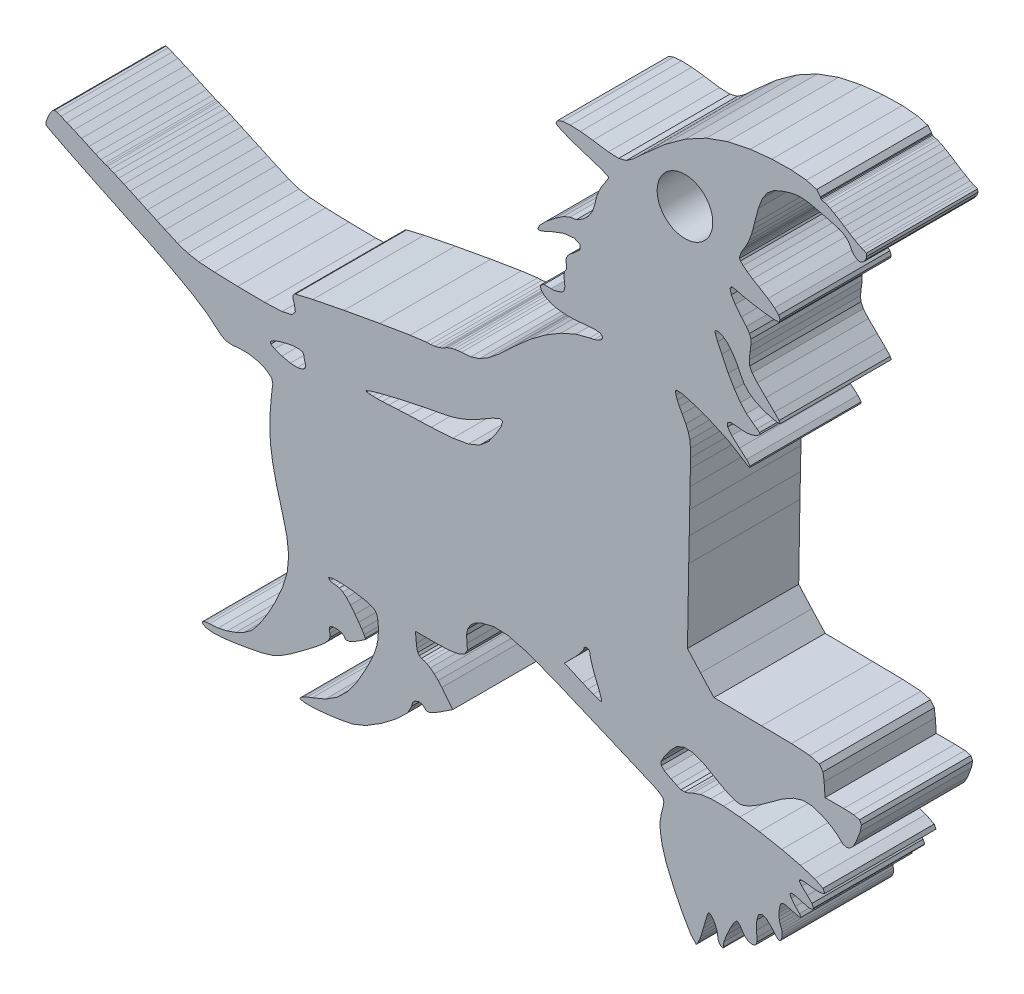
SolidWorks part; units mm, degrees
ref_plane "Plan de face" through (0, 0, 0) normal (0, 0, 1) x (1, 0, 0)
ref_plane "Plan de dessus" through (0, 0, 0) normal (0, 1, 0) x (1, 0, 0)
ref_plane "Plan de droite" through (0, 0, 0) normal (1, 0, 0) x (0, 0, -1)
sketch "Esquisse7" plane through (0, 0, 0) normal (0, 0, 1) x (1, 0, 0)
  line L0 (21.1015, 17.6172) -> (20.7585, 17.1388)
  line L1 (20.7585, 17.1388) -> (20.3691, 16.8087)
  line L2 (20.3691, 16.8087) -> (19.8602, 16.5976)
  line L3 (19.8602, 16.5976) -> (19.1586, 16.4758)
  line L4 (19.1586, 16.4758) -> (18.1909, 16.4138)
  line L5 (18.1909, 16.4138) -> (17.6884, 16.3956)
  line L6 (17.6884, 16.3956) -> (17.1798, 16.3753)
  line L7 (17.1798, 16.3753) -> (16.7028, 16.3544)
  line L8 (16.7028, 16.3544) -> (16.295, 16.3341)
  line L9 (16.295, 16.3341) -> (15.994, 16.3159)
  line L10 (15.994, 16.3159) -> (15.7611, 16.3109)
  line L11 (15.7611, 16.3109) -> (15.5577, 16.3134)
  line L12 (15.5577, 16.3134) -> (15.3966, 16.3239)
  line L13 (15.3966, 16.3239) -> (15.2906, 16.3432)
  line L14 (15.2906, 16.3432) -> (15.2524, 16.3718)
  line L15 (15.2524, 16.3718) -> (15.4756, 16.4659)
  line L16 (15.4756, 16.4659) -> (16.0642, 16.6271)
  line L17 (16.0642, 16.6271) -> (16.8966, 16.8252)
  line L18 (16.8966, 16.8252) -> (17.8513, 17.0301)
  line L19 (17.8513, 17.0301) -> (18.8066, 17.2114)
  line L20 (18.8066, 17.2114) -> (19.1164, 17.2809)
  line L21 (19.1164, 17.2809) -> (19.4476, 17.3847)
  line L22 (19.4476, 17.3847) -> (19.7849, 17.5167)
  line L23 (19.7849, 17.5167) -> (20.1128, 17.6708)
  line L24 (20.1128, 17.6708) -> (20.4158, 17.8411)
  line L25 (20.4158, 17.8411) -> (20.9519, 18.151)
  line L26 (20.9519, 18.151) -> (21.2758, 18.2882)
  line L27 (21.2758, 18.2882) -> (21.4001, 18.2481)
  line L28 (21.4001, 18.2481) -> (21.3378, 18.026)
  line L29 (21.3378, 18.026) -> (21.1015, 17.6172)
  line L30 (12.4538, 16.3858) -> (12.4585, 16.3348)
  line L31 (12.4585, 16.3348) -> (12.4712, 16.2696)
  line L32 (12.4712, 16.2696) -> (12.4901, 16.1964)
  line L33 (12.4901, 16.1964) -> (12.5129, 16.1212)
  line L34 (12.5129, 16.1212) -> (12.5377, 16.05)
  line L35 (12.5377, 16.05) -> (12.5346, 15.8897)
  line L36 (12.5346, 15.8897) -> (12.4052, 15.7818)
  line L37 (12.4052, 15.7818) -> (12.171, 15.7316)
  line L38 (12.171, 15.7316) -> (11.8535, 15.7446)
  line L39 (11.8535, 15.7446) -> (11.4743, 15.8261)
  line L40 (11.4743, 15.8261) -> (11.1484, 15.9417)
  line L41 (11.1484, 15.9417) -> (10.9763, 16.0426)
  line L42 (10.9763, 16.0426) -> (10.9574, 16.1374)
  line L43 (10.9574, 16.1374) -> (11.091, 16.2349)
  line L44 (11.091, 16.2349) -> (11.3763, 16.3438)
  line L45 (11.3763, 16.3438) -> (11.7087, 16.4328)
  line L46 (11.7087, 16.4328) -> (12.0034, 16.4815)
  line L47 (12.0034, 16.4815) -> (12.2397, 16.4899)
  line L48 (12.2397, 16.4899) -> (12.3968, 16.458)
  line L49 (12.3968, 16.458) -> (12.4538, 16.3858)
  line L50 (25.3274, 11.1384) -> (25.3417, 11.0402)
  line L51 (25.3417, 11.0402) -> (25.3815, 10.8895)
  line L52 (25.3815, 10.8895) -> (25.4422, 10.7012)
  line L53 (25.4422, 10.7012) -> (25.519, 10.4901)
  line L54 (25.519, 10.4901) -> (25.6072, 10.2709)
  line L55 (25.6072, 10.2709) -> (25.6938, 10.0596)
  line L56 (25.6938, 10.0596) -> (25.7655, 9.8706)
  line L57 (25.7655, 9.8706) -> (25.8178, 9.7157)
  line L58 (25.8178, 9.7157) -> (25.8459, 9.6073)
  line L59 (25.8459, 9.6073) -> (25.8451, 9.5572)
  line L60 (25.8451, 9.5572) -> (25.7872, 9.5597)
  line L61 (25.7872, 9.5597) -> (25.6575, 9.5971)
  line L62 (25.6575, 9.5971) -> (25.4713, 9.664)
  line L63 (25.4713, 9.664) -> (25.2442, 9.7551)
  line L64 (25.2442, 9.7551) -> (24.9915, 9.8651)
  line L65 (24.9915, 9.8651) -> (24.1799, 10.2289)
  line L66 (24.1799, 10.2289) -> (24.6137, 10.6627)
  line L67 (24.6137, 10.6627) -> (24.7502, 10.8109)
  line L68 (24.7502, 10.8109) -> (24.8692, 10.9484)
  line L69 (24.8692, 10.9484) -> (24.9633, 11.0677)
  line L70 (24.9633, 11.0677) -> (25.0252, 11.1615)
  line L71 (25.0252, 11.1615) -> (25.0475, 11.2224)
  line L72 (25.0475, 11.2224) -> (25.0553, 11.2555)
  line L73 (25.0553, 11.2555) -> (25.0766, 11.286)
  line L74 (25.0766, 11.286) -> (25.108, 11.3111)
  line L75 (25.108, 11.3111) -> (25.146, 11.3281)
  line L76 (25.146, 11.3281) -> (25.1874, 11.3343)
  line L77 (25.1874, 11.3343) -> (25.2342, 11.3247)
  line L78 (25.2342, 11.3247) -> (25.273, 11.2976)
  line L79 (25.273, 11.2976) -> (25.3023, 11.2558)
  line L80 (25.3023, 11.2558) -> (25.3209, 11.2018)
  line L81 (25.3209, 11.2018) -> (25.3274, 11.1384)
  line L82 (32.5338, 34.4088) -> (31.5038, 34.1932)
  line L83 (31.5038, 34.1932) -> (30.5503, 33.8493)
  line L84 (30.5503, 33.8493) -> (29.6291, 33.353)
  line L85 (29.6291, 33.353) -> (28.6959, 32.68)
  line L86 (28.6959, 32.68) -> (27.7062, 31.8061)
  line L87 (27.7062, 31.8061) -> (27.2851, 31.4119)
  line L88 (27.2851, 31.4119) -> (26.9575, 31.1842)
  line L89 (26.9575, 31.1842) -> (26.6151, 31.0948)
  line L90 (26.6151, 31.0948) -> (26.1497, 31.1157)
  line L91 (26.1497, 31.1157) -> (25.4533, 31.2184)
  line L92 (25.4533, 31.2184) -> (24.8986, 31.2857)
  line L93 (24.8986, 31.2857) -> (24.438, 31.3033)
  line L94 (24.438, 31.3033) -> (24.0881, 31.2718)
  line L95 (24.0881, 31.2718) -> (23.8659, 31.192)
  line L96 (23.8659, 31.192) -> (23.7881, 31.0645)
  line L97 (23.7881, 31.0645) -> (23.8487, 31.0054)
  line L98 (23.8487, 31.0054) -> (24.0174, 30.9174)
  line L99 (24.0174, 30.9174) -> (24.2747, 30.8086)
  line L100 (24.2747, 30.8086) -> (24.6013, 30.687)
  line L101 (24.6013, 30.687) -> (24.9775, 30.5607)
  line L102 (24.9775, 30.5607) -> (25.3538, 30.4444)
  line L103 (25.3538, 30.4444) -> (25.6803, 30.3355)
  line L104 (25.6803, 30.3355) -> (25.9377, 30.2414)
  line L105 (25.9377, 30.2414) -> (26.1064, 30.1694)
  line L106 (26.1064, 30.1694) -> (26.1669, 30.127)
  line L107 (26.1669, 30.127) -> (26.1527, 30.0913)
  line L108 (26.1527, 30.0913) -> (26.1137, 30.0226)
  line L109 (26.1137, 30.0226) -> (26.0551, 29.9285)
  line L110 (26.0551, 29.9285) -> (25.9825, 29.8162)
  line L111 (25.9825, 29.8162) -> (25.9011, 29.6932)
  line L112 (25.9011, 29.6932) -> (25.8096, 29.5463)
  line L113 (25.8096, 29.5463) -> (25.7235, 29.3679)
  line L114 (25.7235, 29.3679) -> (25.6482, 29.1733)
  line L115 (25.6482, 29.1733) -> (25.589, 28.9781)
  line L116 (25.589, 28.9781) -> (25.5512, 28.7976)
  line L117 (25.5512, 28.7976) -> (25.4441, 28.4638)
  line L118 (25.4441, 28.4638) -> (25.255, 28.1656)
  line L119 (25.255, 28.1656) -> (25.0062, 27.9251)
  line L120 (25.0062, 27.9251) -> (24.7197, 27.7646)
  line L121 (24.7197, 27.7646) -> (24.4178, 27.7062)
  line L122 (24.4178, 27.7062) -> (24.1416, 27.5959)
  line L123 (24.1416, 27.5959) -> (23.7432, 27.3278)
  line L124 (23.7432, 27.3278) -> (23.3388, 26.9959)
  line L125 (23.3388, 26.9959) -> (23.0445, 26.6942)
  line L126 (23.0445, 26.6942) -> (22.9765, 26.5168)
  line L127 (22.9765, 26.5168) -> (23.0216, 26.5077)
  line L128 (23.0216, 26.5077) -> (23.1158, 26.5282)
  line L129 (23.1158, 26.5282) -> (23.2476, 26.5742)
  line L130 (23.2476, 26.5742) -> (23.4055, 26.6417)
  line L131 (23.4055, 26.6417) -> (23.5782, 26.7267)
  line L132 (23.5782, 26.7267) -> (24.1555, 26.9427)
  line L133 (24.1555, 26.9427) -> (24.6133, 26.9875)
  line L134 (24.6133, 26.9875) -> (24.8789, 26.8879)
  line L135 (24.8789, 26.8879) -> (24.8799, 26.6707)
  line L136 (24.8799, 26.6707) -> (24.5438, 26.3628)
  line L137 (24.5438, 26.3628) -> (24.4178, 26.2675)
  line L138 (24.4178, 26.2675) -> (24.3255, 26.1674)
  line L139 (24.3255, 26.1674) -> (24.2667, 26.0646)
  line L140 (24.2667, 26.0646) -> (24.2415, 25.9612)
  line L141 (24.2415, 25.9612) -> (24.2499, 25.8591)
  line L142 (24.2499, 25.8591) -> (24.2685, 25.7759)
  line L143 (24.2685, 25.7759) -> (24.2743, 25.6974)
  line L144 (24.2743, 25.6974) -> (24.268, 25.6284)
  line L145 (24.268, 25.6284) -> (24.2503, 25.5734)
  line L146 (24.2503, 25.5734) -> (24.2219, 25.5373)
  line L147 (24.2219, 25.5373) -> (24.192, 25.4999)
  line L148 (24.192, 25.4999) -> (24.1709, 25.4262)
  line L149 (24.1709, 25.4262) -> (24.1605, 25.3237)
  line L150 (24.1605, 25.3237) -> (24.1628, 25.1996)
  line L151 (24.1628, 25.1996) -> (24.1799, 25.0615)
  line L152 (24.1799, 25.0615) -> (24.1943, 24.8991)
  line L153 (24.1943, 24.8991) -> (24.1837, 24.7763)
  line L154 (24.1837, 24.7763) -> (24.1437, 24.6857)
  line L155 (24.1437, 24.6857) -> (24.0693, 24.62)
  line L156 (24.0693, 24.62) -> (23.956, 24.5717)
  line L157 (23.956, 24.5717) -> (23.8616, 24.5416)
  line L158 (23.8616, 24.5416) -> (23.7678, 24.5189)
  line L159 (23.7678, 24.5189) -> (23.682, 24.5042)
  line L160 (23.682, 24.5042) -> (23.6117, 24.4983)
  line L161 (23.6117, 24.4983) -> (23.5642, 24.5018)
  line L162 (23.5642, 24.5018) -> (23.2568, 24.5052)
  line L163 (23.2568, 24.5052) -> (23.1066, 24.4086)
  line L164 (23.1066, 24.4086) -> (23.1129, 24.2529)
  line L165 (23.1129, 24.2529) -> (23.275, 24.0791)
  line L166 (23.275, 24.0791) -> (23.5922, 23.9281)
  line L167 (23.5922, 23.9281) -> (23.8063, 23.8711)
  line L168 (23.8063, 23.8711) -> (24.0586, 23.8349)
  line L169 (24.0586, 23.8349) -> (24.3438, 23.8203)
  line L170 (24.3438, 23.8203) -> (24.6566, 23.8278)
  line L171 (24.6566, 23.8278) -> (24.9915, 23.8581)
  line L172 (24.9915, 23.8581) -> (25.3641, 23.8894)
  line L173 (25.3641, 23.8894) -> (25.6211, 23.8973)
  line L174 (25.6211, 23.8973) -> (25.7814, 23.8782)
  line L175 (25.7814, 23.8782) -> (25.8638, 23.829)
  line L176 (25.8638, 23.829) -> (25.8871, 23.7461)
  line L177 (25.8871, 23.7461) -> (25.8623, 23.6726)
  line L178 (25.8623, 23.6726) -> (25.7899, 23.6044)
  line L179 (25.7899, 23.6044) -> (25.6725, 23.5436)
  line L180 (25.6725, 23.5436) -> (25.5127, 23.4923)
  line L181 (25.5127, 23.4923) -> (25.3134, 23.4523)
  line L182 (25.3134, 23.4523) -> (24.6855, 23.2854)
  line L183 (24.6855, 23.2854) -> (24.018, 22.9902)
  line L184 (24.018, 22.9902) -> (23.3215, 22.5728)
  line L185 (23.3215, 22.5728) -> (22.607, 22.0391)
  line L186 (22.607, 22.0391) -> (21.8851, 21.3953)
  line L187 (21.8851, 21.3953) -> (21.2619, 20.8106)
  line L188 (21.2619, 20.8106) -> (20.7683, 20.412)
  line L189 (20.7683, 20.412) -> (20.3527, 20.1672)
  line L190 (20.3527, 20.1672) -> (19.9632, 20.0439)
  line L191 (19.9632, 20.0439) -> (19.5482, 20.01)
  line L192 (19.5482, 20.01) -> (19.3892, 20.0004)
  line L193 (19.3892, 20.0004) -> (19.2227, 19.9733)
  line L194 (19.2227, 19.9733) -> (19.0616, 19.9314)
  line L195 (19.0616, 19.9314) -> (18.9187, 19.8775)
  line L196 (18.9187, 19.8775) -> (18.8066, 19.8141)
  line L197 (18.8066, 19.8141) -> (18.6897, 19.7494)
  line L198 (18.6897, 19.7494) -> (18.5332, 19.6928)
  line L199 (18.5332, 19.6928) -> (18.3512, 19.6489)
  line L200 (18.3512, 19.6489) -> (18.1578, 19.6225)
  line L201 (18.1578, 19.6225) -> (17.967, 19.6182)
  line L202 (17.967, 19.6182) -> (17.2375, 19.525)
  line L203 (17.2375, 19.525) -> (15.8652, 19.2954)
  line L204 (15.8652, 19.2954) -> (14.2685, 19.0046)
  line L205 (14.2685, 19.0046) -> (12.866, 18.728)
  line L206 (12.866, 18.728) -> (12.076, 18.5407)
  line L207 (12.076, 18.5407) -> (12.0138, 18.5066)
  line L208 (12.0138, 18.5066) -> (11.9786, 18.4523)
  line L209 (11.9786, 18.4523) -> (11.9702, 18.3745)
  line L210 (11.9702, 18.3745) -> (11.9887, 18.2698)
  line L211 (11.9887, 18.2698) -> (12.034, 18.1349)
  line L212 (12.034, 18.1349) -> (12.0808, 17.8481)
  line L213 (12.0808, 17.8481) -> (11.9214, 17.6641)
  line L214 (11.9214, 17.6641) -> (11.4839, 17.5647)
  line L215 (11.4839, 17.5647) -> (10.6965, 17.5318)
  line L216 (10.6965, 17.5318) -> (9.4873, 17.5472)
  line L217 (9.4873, 17.5472) -> (8.4429, 17.58)
  line L218 (8.4429, 17.58) -> (7.7452, 17.6283)
  line L219 (7.7452, 17.6283) -> (7.2436, 17.7175)
  line L220 (7.2436, 17.7175) -> (6.7876, 17.8732)
  line L221 (6.7876, 17.8732) -> (6.2269, 18.121)
  line L222 (6.2269, 18.121) -> (5.8359, 18.2997)
  line L223 (5.8359, 18.2997) -> (5.4227, 18.4899)
  line L224 (5.4227, 18.4899) -> (5.0189, 18.6761)
  line L225 (5.0189, 18.6761) -> (4.6561, 18.8428)
  line L226 (4.6561, 18.8428) -> (4.3658, 18.9745)
  line L227 (4.3658, 18.9745) -> (4.1311, 19.0793)
  line L228 (4.1311, 19.0793) -> (3.9219, 19.1713)
  line L229 (3.9219, 19.1713) -> (3.7502, 19.2445)
  line L230 (3.7502, 19.2445) -> (3.6283, 19.2929)
  line L231 (3.6283, 19.2929) -> (3.5682, 19.3104)
  line L232 (3.5682, 19.3104) -> (3.4976, 19.3358)
  line L233 (3.4976, 19.3358) -> (3.3322, 19.4062)
  line L234 (3.3322, 19.4062) -> (3.0917, 19.5129)
  line L235 (3.0917, 19.5129) -> (2.7954, 19.6471)
  line L236 (2.7954, 19.6471) -> (2.4628, 19.8001)
  line L237 (2.4628, 19.8001) -> (2.1187, 19.9531)
  line L238 (2.1187, 19.9531) -> (1.8054, 20.0874)
  line L239 (1.8054, 20.0874) -> (1.5439, 20.1941)
  line L240 (1.5439, 20.1941) -> (1.355, 20.2645)
  line L241 (1.355, 20.2645) -> (1.2594, 20.2899)
  line L242 (1.2594, 20.2899) -> (1.1569, 20.2178)
  line L243 (1.1569, 20.2178) -> (1.0377, 20.0423)
  line L244 (1.0377, 20.0423) -> (0.9319, 19.8244)
  line L245 (0.9319, 19.8244) -> (0.8698, 19.6254)
  line L246 (0.8698, 19.6254) -> (0.8816, 19.5063)
  line L247 (0.8816, 19.5063) -> (1.1273, 19.3715)
  line L248 (1.1273, 19.3715) -> (1.7055, 19.0795)
  line L249 (1.7055, 19.0795) -> (2.4784, 18.6983)
  line L250 (2.4784, 18.6983) -> (3.3085, 18.2955)
  line L251 (3.3085, 18.2955) -> (4.058, 17.939)
  line L252 (4.058, 17.939) -> (5.5155, 17.2485)
  line L253 (5.5155, 17.2485) -> (6.6372, 16.6828)
  line L254 (6.6372, 16.6828) -> (7.4835, 16.2092)
  line L255 (7.4835, 16.2092) -> (8.1148, 15.7946)
  line L256 (8.1148, 15.7946) -> (8.5917, 15.4063)
  line L257 (8.5917, 15.4063) -> (8.7497, 15.2728)
  line L258 (8.7497, 15.2728) -> (8.9016, 15.1876)
  line L259 (8.9016, 15.1876) -> (9.0683, 15.1454)
  line L260 (9.0683, 15.1454) -> (9.2705, 15.1408)
  line L261 (9.2705, 15.1408) -> (9.5292, 15.1684)
  line L262 (9.5292, 15.1684) -> (9.9728, 15.1741)
  line L263 (9.9728, 15.1741) -> (10.4076, 15.0898)
  line L264 (10.4076, 15.0898) -> (10.7745, 14.9397)
  line L265 (10.7745, 14.9397) -> (11.0145, 14.748)
  line L266 (11.0145, 14.748) -> (11.0685, 14.5387)
  line L267 (11.0685, 14.5387) -> (11.0487, 14.4228)
  line L268 (11.0487, 14.4228) -> (11.0241, 14.2222)
  line L269 (11.0241, 14.2222) -> (10.9969, 13.9564)
  line L270 (10.9969, 13.9564) -> (10.9691, 13.645)
  line L271 (10.9691, 13.645) -> (10.9425, 13.3074)
  line L272 (10.9425, 13.3074) -> (10.9308, 12.6907)
  line L273 (10.9308, 12.6907) -> (10.9694, 12.0813)
  line L274 (10.9694, 12.0813) -> (11.0685, 11.4264)
  line L275 (11.0685, 11.4264) -> (11.2381, 10.6726)
  line L276 (11.2381, 10.6726) -> (11.4883, 9.7671)
  line L277 (11.4883, 9.7671) -> (11.7005, 8.9207)
  line L278 (11.7005, 8.9207) -> (11.7791, 8.208)
  line L279 (11.7791, 8.208) -> (11.718, 7.5476)
  line L280 (11.718, 7.5476) -> (11.5111, 6.8584)
  line L281 (11.5111, 6.8584) -> (11.1524, 6.059)
  line L282 (11.1524, 6.059) -> (10.9289, 5.6403)
  line L283 (10.9289, 5.6403) -> (10.6906, 5.2418)
  line L284 (10.6906, 5.2418) -> (10.4563, 4.8903)
  line L285 (10.4563, 4.8903) -> (10.2448, 4.6127)
  line L286 (10.2448, 4.6127) -> (10.075, 4.4358)
  line L287 (10.075, 4.4358) -> (9.7659, 4.2169)
  line L288 (9.7659, 4.2169) -> (9.4058, 4.035)
  line L289 (9.4058, 4.035) -> (9.0141, 3.8968)
  line L290 (9.0141, 3.8968) -> (8.6103, 3.8089)
  line L291 (8.6103, 3.8089) -> (8.2139, 3.7781)
  line L292 (8.2139, 3.7781) -> (8.0905, 3.7716)
  line L293 (8.0905, 3.7716) -> (7.9927, 3.753)
  line L294 (7.9927, 3.753) -> (7.9258, 3.7237)
  line L295 (7.9258, 3.7237) -> (7.8951, 3.685)
  line L296 (7.8951, 3.685) -> (7.9061, 3.6382)
  line L297 (7.9061, 3.6382) -> (8.0524, 3.5475)
  line L298 (8.0524, 3.5475) -> (8.3411, 3.5106)
  line L299 (8.3411, 3.5106) -> (8.7735, 3.5274)
  line L300 (8.7735, 3.5274) -> (9.351, 3.5979)
  line L301 (9.351, 3.5979) -> (10.075, 3.7221)
  line L302 (10.075, 3.7221) -> (10.6167, 3.8334)
  line L303 (10.6167, 3.8334) -> (11.0402, 3.9608)
  line L304 (11.0402, 3.9608) -> (11.4321, 4.1473)
  line L305 (11.4321, 4.1473) -> (11.8791, 4.4359)
  line L306 (11.8791, 4.4359) -> (12.4678, 4.8696)
  line L307 (12.4678, 4.8696) -> (13.0037, 5.2785)
  line L308 (13.0037, 5.2785) -> (13.3562, 5.5719)
  line L309 (13.3562, 5.5719) -> (13.5569, 5.7854)
  line L310 (13.5569, 5.7854) -> (13.6374, 5.9545)
  line L311 (13.6374, 5.9545) -> (13.6292, 6.1149)
  line L312 (13.6292, 6.1149) -> (13.6018, 6.2505)
  line L313 (13.6018, 6.2505) -> (13.6079, 6.3431)
  line L314 (13.6079, 6.3431) -> (13.6544, 6.4001)
  line L315 (13.6544, 6.4001) -> (13.7479, 6.4288)
  line L316 (13.7479, 6.4288) -> (13.8951, 6.4368)
  line L317 (13.8951, 6.4368) -> (14.0098, 6.4287)
  line L318 (14.0098, 6.4287) -> (14.1145, 6.4059)
  line L319 (14.1145, 6.4059) -> (14.2024, 6.3703)
  line L320 (14.2024, 6.3703) -> (14.2667, 6.3239)
  line L321 (14.2667, 6.3239) -> (14.3009, 6.2689)
  line L322 (14.3009, 6.2689) -> (14.3634, 6.217)
  line L323 (14.3634, 6.217) -> (14.4858, 6.2304)
  line L324 (14.4858, 6.2304) -> (14.6706, 6.3102)
  line L325 (14.6706, 6.3102) -> (14.9206, 6.4578)
  line L326 (14.9206, 6.4578) -> (15.2384, 6.6747)
  line L327 (15.2384, 6.6747) -> (15.2279, 6.7196)
  line L328 (15.2279, 6.7196) -> (15.1676, 6.8289)
  line L329 (15.1676, 6.8289) -> (15.0651, 6.99)
  line L330 (15.0651, 6.99) -> (14.9276, 7.1901)
  line L331 (14.9276, 7.1901) -> (14.7626, 7.4163)
  line L332 (14.7626, 7.4163) -> (14.5583, 7.6825)
  line L333 (14.5583, 7.6825) -> (14.3775, 7.8802)
  line L334 (14.3775, 7.8802) -> (14.2135, 8.0148)
  line L335 (14.2135, 8.0148) -> (14.0596, 8.0915)
  line L336 (14.0596, 8.0915) -> (13.9091, 8.1159)
  line L337 (13.9091, 8.1159) -> (13.8043, 8.1224)
  line L338 (13.8043, 8.1224) -> (13.7123, 8.141)
  line L339 (13.7123, 8.141) -> (13.639, 8.1704)
  line L340 (13.639, 8.1704) -> (13.5907, 8.2091)
  line L341 (13.5907, 8.2091) -> (13.5732, 8.2559)
  line L342 (13.5732, 8.2559) -> (13.7449, 8.3163)
  line L343 (13.7449, 8.3163) -> (14.1679, 8.3197)
  line L344 (14.1679, 8.3197) -> (14.7036, 8.276)
  line L345 (14.7036, 8.276) -> (15.2139, 8.1954)
  line L346 (15.2139, 8.1954) -> (15.5602, 8.088)
  line L347 (15.5602, 8.088) -> (15.6617, 8.021)
  line L348 (15.6617, 8.021) -> (15.7335, 7.9151)
  line L349 (15.7335, 7.9151) -> (15.7799, 7.7615)
  line L350 (15.7799, 7.7615) -> (15.8047, 7.5515)
  line L351 (15.8047, 7.5515) -> (15.8121, 7.2764)
  line L352 (15.8121, 7.2764) -> (15.7952, 6.973)
  line L353 (15.7952, 6.973) -> (15.7373, 6.6663)
  line L354 (15.7373, 6.6663) -> (15.6277, 6.3293)
  line L355 (15.6277, 6.3293) -> (15.4557, 5.9353)
  line L356 (15.4557, 5.9353) -> (15.2104, 5.4573)
  line L357 (15.2104, 5.4573) -> (14.8152, 4.7636)
  line L358 (14.8152, 4.7636) -> (14.4033, 4.2129)
  line L359 (14.4033, 4.2129) -> (13.951, 3.7838)
  line L360 (13.951, 3.7838) -> (13.435, 3.4548)
  line L361 (13.435, 3.4548) -> (12.8316, 3.2044)
  line L362 (12.8316, 3.2044) -> (12.6232, 3.1266)
  line L363 (12.6232, 3.1266) -> (12.457, 3.0488)
  line L364 (12.457, 3.0488) -> (12.342, 2.9777)
  line L365 (12.342, 2.9777) -> (12.2867, 2.9201)
  line L366 (12.2867, 2.9201) -> (12.2999, 2.8826)
  line L367 (12.2999, 2.8826) -> (12.523, 2.8413)
  line L368 (12.523, 2.8413) -> (12.9429, 2.8476)
  line L369 (12.9429, 2.8476) -> (13.4877, 2.8957)
  line L370 (13.4877, 2.8957) -> (14.0856, 2.9793)
  line L371 (14.0856, 2.9793) -> (14.6647, 3.0925)
  line L372 (14.6647, 3.0925) -> (15.2447, 3.3289)
  line L373 (15.2447, 3.3289) -> (15.9462, 3.7614)
  line L374 (15.9462, 3.7614) -> (16.6222, 4.2773)
  line L375 (16.6222, 4.2773) -> (17.1257, 4.7636)
  line L376 (17.1257, 4.7636) -> (17.3094, 5.1075)
  line L377 (17.3094, 5.1075) -> (17.3451, 5.273)
  line L378 (17.3451, 5.273) -> (17.4607, 5.3909)
  line L379 (17.4607, 5.3909) -> (17.6187, 5.447)
  line L380 (17.6187, 5.447) -> (17.7813, 5.4272)
  line L381 (17.7813, 5.4272) -> (17.9111, 5.3173)
  line L382 (17.9111, 5.3173) -> (17.9688, 5.2653)
  line L383 (17.9688, 5.2653) -> (18.0608, 5.2603)
  line L384 (18.0608, 5.2603) -> (18.1911, 5.3022)
  line L385 (18.1911, 5.3022) -> (18.3638, 5.3912)
  line L386 (18.3638, 5.3912) -> (18.5827, 5.5272)
  line L387 (18.5827, 5.5272) -> (19.1564, 5.9051)
  line L388 (19.1564, 5.9051) -> (18.6667, 6.5207)
  line L389 (18.6667, 6.5207) -> (18.4978, 6.7086)
  line L390 (18.4978, 6.7086) -> (18.3194, 6.8783)
  line L391 (18.3194, 6.8783) -> (18.1458, 7.0184)
  line L392 (18.1458, 7.0184) -> (17.991, 7.1176)
  line L393 (17.991, 7.1176) -> (17.8691, 7.1644)
  line L394 (17.8691, 7.1644) -> (17.744, 7.194)
  line L395 (17.744, 7.194) -> (17.6512, 7.2531)
  line L396 (17.6512, 7.2531) -> (17.586, 7.3478)
  line L397 (17.586, 7.3478) -> (17.5435, 7.4841)
  line L398 (17.5435, 7.4841) -> (17.5193, 7.6682)
  line L399 (17.5193, 7.6682) -> (17.4773, 8.1159)
  line L400 (17.4773, 8.1159) -> (18.4008, 8.1159)
  line L401 (18.4008, 8.1159) -> (19.0138, 8.1377)
  line L402 (19.0138, 8.1377) -> (19.4394, 8.2091)
  line L403 (19.4394, 8.2091) -> (19.6985, 8.3396)
  line L404 (19.6985, 8.3396) -> (19.8118, 8.5387)
  line L405 (19.8118, 8.5387) -> (19.8001, 8.8156)
  line L406 (19.8001, 8.8156) -> (19.773, 9.1159)
  line L407 (19.773, 9.1159) -> (19.8252, 9.378)
  line L408 (19.8252, 9.378) -> (19.9553, 9.6004)
  line L409 (19.9553, 9.6004) -> (20.1619, 9.7819)
  line L410 (20.1619, 9.7819) -> (20.4438, 9.921)
  line L411 (20.4438, 9.921) -> (21.0025, 10.0569)
  line L412 (21.0025, 10.0569) -> (21.6257, 10.0343)
  line L413 (21.6257, 10.0343) -> (22.4719, 9.8122)
  line L414 (22.4719, 9.8122) -> (23.6996, 9.3497)
  line L415 (23.6996, 9.3497) -> (25.4673, 8.6057)
  line L416 (25.4673, 8.6057) -> (25.896, 8.4236)
  line L417 (25.896, 8.4236) -> (26.3684, 8.2233)
  line L418 (26.3684, 8.2233) -> (26.8476, 8.0203)
  line L419 (26.8476, 8.0203) -> (27.2965, 7.8302)
  line L420 (27.2965, 7.8302) -> (27.6782, 7.6682)
  line L421 (27.6782, 7.6682) -> (28.1599, 7.463)
  line L422 (28.1599, 7.463) -> (28.4555, 7.3129)
  line L423 (28.4555, 7.3129) -> (28.6041, 7.1856)
  line L424 (28.6041, 7.1856) -> (28.6445, 7.0489)
  line L425 (28.6445, 7.0489) -> (28.6157, 6.8706)
  line L426 (28.6157, 6.8706) -> (28.5281, 6.5183)
  line L427 (28.5281, 6.5183) -> (28.4821, 6.2453)
  line L428 (28.4821, 6.2453) -> (28.4757, 5.993)
  line L429 (28.4757, 5.993) -> (28.5069, 5.7032)
  line L430 (28.5069, 5.7032) -> (28.5737, 5.3173)
  line L431 (28.5737, 5.3173) -> (28.7539, 4.7285)
  line L432 (28.7539, 4.7285) -> (29.0945, 3.9315)
  line L433 (29.0945, 3.9315) -> (29.4976, 3.121)
  line L434 (29.4976, 3.121) -> (29.8651, 2.4919)
  line L435 (29.8651, 2.4919) -> (30.099, 2.2389)
  line L436 (30.099, 2.2389) -> (30.1333, 2.2692)
  line L437 (30.1333, 2.2692) -> (30.1825, 2.354)
  line L438 (30.1825, 2.354) -> (30.241, 2.4837)
  line L439 (30.241, 2.4837) -> (30.3036, 2.649)
  line L440 (30.3036, 2.649) -> (30.3648, 2.8406)
  line L441 (30.3648, 2.8406) -> (30.4232, 3.0364)
  line L442 (30.4232, 3.0364) -> (30.4788, 3.2281)
  line L443 (30.4788, 3.2281) -> (30.5291, 3.4018)
  line L444 (30.5291, 3.4018) -> (30.5713, 3.5431)
  line L445 (30.5713, 3.5431) -> (30.6027, 3.6382)
  line L446 (30.6027, 3.6382) -> (30.6357, 3.7183)
  line L447 (30.6357, 3.7183) -> (30.6721, 3.7555)
  line L448 (30.6721, 3.7555) -> (30.7186, 3.747)
  line L449 (30.7186, 3.747) -> (30.7818, 3.6901)
  line L450 (30.7818, 3.6901) -> (30.8686, 3.5822)
  line L451 (30.8686, 3.5822) -> (30.932, 3.4814)
  line L452 (30.932, 3.4814) -> (30.9859, 3.3697)
  line L453 (30.9859, 3.3697) -> (31.0278, 3.2568)
  line L454 (31.0278, 3.2568) -> (31.0549, 3.1519)
  line L455 (31.0549, 3.1519) -> (31.0645, 3.0645)
  line L456 (31.0645, 3.0645) -> (31.0723, 2.9798)
  line L457 (31.0723, 2.9798) -> (31.0936, 2.8979)
  line L458 (31.0936, 2.8979) -> (31.1249, 2.8247)
  line L459 (31.1249, 2.8247) -> (31.163, 2.7663)
  line L460 (31.163, 2.7663) -> (31.2044, 2.7286)
  line L461 (31.2044, 2.7286) -> (31.2497, 2.7033)
  line L462 (31.2497, 2.7033) -> (31.2841, 2.6942)
  line L463 (31.2841, 2.6942) -> (31.3072, 2.7004)
  line L464 (31.3072, 2.7004) -> (31.3182, 2.7215)
  line L465 (31.3182, 2.7215) -> (31.3164, 2.7566)
  line L466 (31.3164, 2.7566) -> (31.3454, 2.9564)
  line L467 (31.3454, 2.9564) -> (31.4677, 3.2872)
  line L468 (31.4677, 3.2872) -> (31.6357, 3.6483)
  line L469 (31.6357, 3.6483) -> (31.8018, 3.9388)
  line L470 (31.8018, 3.9388) -> (31.9181, 4.058)
  line L471 (31.9181, 4.058) -> (31.9645, 4.0436)
  line L472 (31.9645, 4.0436) -> (32.0177, 4.0038)
  line L473 (32.0177, 4.0038) -> (32.0742, 3.9431)
  line L474 (32.0742, 3.9431) -> (32.1308, 3.8663)
  line L475 (32.1308, 3.8663) -> (32.1839, 3.7781)
  line L476 (32.1839, 3.7781) -> (32.2451, 3.6899)
  line L477 (32.2451, 3.6899) -> (32.3236, 3.6131)
  line L478 (32.3236, 3.6131) -> (32.4136, 3.5524)
  line L479 (32.4136, 3.5524) -> (32.509, 3.5126)
  line L480 (32.509, 3.5126) -> (32.6037, 3.4983)
  line L481 (32.6037, 3.4983) -> (32.7156, 3.5128)
  line L482 (32.7156, 3.5128) -> (32.7864, 3.5677)
  line L483 (32.7864, 3.5677) -> (32.8224, 3.6796)
  line L484 (32.8224, 3.6796) -> (32.8294, 3.8654)
  line L485 (32.8294, 3.8654) -> (32.8136, 4.1419)
  line L486 (32.8136, 4.1419) -> (32.822, 4.5509)
  line L487 (32.822, 4.5509) -> (32.9077, 4.8006)
  line L488 (32.9077, 4.8006) -> (33.0605, 4.8865)
  line L489 (33.0605, 4.8865) -> (33.2704, 4.8037)
  line L490 (33.2704, 4.8037) -> (33.5273, 4.5477)
  line L491 (33.5273, 4.5477) -> (33.6648, 4.3824)
  line L492 (33.6648, 4.3824) -> (33.7648, 4.2862)
  line L493 (33.7648, 4.2862) -> (33.8366, 4.2545)
  line L494 (33.8366, 4.2545) -> (33.8895, 4.2826)
  line L495 (33.8895, 4.2826) -> (33.9331, 4.3658)
  line L496 (33.9331, 4.3658) -> (33.9584, 4.4501)
  line L497 (33.9584, 4.4501) -> (33.9675, 4.5465)
  line L498 (33.9675, 4.5465) -> (33.9613, 4.6469)
  line L499 (33.9613, 4.6469) -> (33.9402, 4.7433)
  line L500 (33.9402, 4.7433) -> (33.9051, 4.8276)
  line L501 (33.9051, 4.8276) -> (33.8669, 4.9199)
  line L502 (33.8669, 4.9199) -> (33.8381, 5.0392)
  line L503 (33.8381, 5.0392) -> (33.8215, 5.1752)
  line L504 (33.8215, 5.1752) -> (33.8196, 5.3179)
  line L505 (33.8196, 5.3179) -> (33.8351, 5.4573)
  line L506 (33.8351, 5.4573) -> (33.8686, 5.6354)
  line L507 (33.8686, 5.6354) -> (33.9148, 5.7403)
  line L508 (33.9148, 5.7403) -> (33.9933, 5.7827)
  line L509 (33.9933, 5.7827) -> (34.1235, 5.7734)
  line L510 (34.1235, 5.7734) -> (34.3249, 5.7231)
  line L511 (34.3249, 5.7231) -> (34.6169, 5.6443)
  line L512 (34.6169, 5.6443) -> (34.7773, 5.6166)
  line L513 (34.7773, 5.6166) -> (34.8155, 5.6506)
  line L514 (34.8155, 5.6506) -> (34.7409, 5.7572)
  line L515 (34.7409, 5.7572) -> (34.5628, 5.947)
  line L516 (34.5628, 5.947) -> (34.3782, 6.1673)
  line L517 (34.3782, 6.1673) -> (34.3118, 6.3091)
  line L518 (34.3118, 6.3091) -> (34.3643, 6.3742)
  line L519 (34.3643, 6.3742) -> (34.5363, 6.3648)
  line L520 (34.5363, 6.3648) -> (34.8286, 6.2829)
  line L521 (34.8286, 6.2829) -> (35.1317, 6.2011)
  line L522 (35.1317, 6.2011) -> (35.3151, 6.2034)
  line L523 (35.3151, 6.2034) -> (35.3737, 6.2829)
  line L524 (35.3737, 6.2829) -> (35.3019, 6.4329)
  line L525 (35.3019, 6.4329) -> (35.0945, 6.6467)
  line L526 (35.0945, 6.6467) -> (34.8499, 6.873)
  line L527 (34.8499, 6.873) -> (34.7396, 7.0201)
  line L528 (34.7396, 7.0201) -> (34.767, 7.096)
  line L529 (34.767, 7.096) -> (34.9355, 7.1088)
  line L530 (34.9355, 7.1088) -> (35.2484, 7.0665)
  line L531 (35.2484, 7.0665) -> (35.4281, 7.048)
  line L532 (35.4281, 7.048) -> (35.591, 7.043)
  line L533 (35.591, 7.043) -> (35.727, 7.0514)
  line L534 (35.727, 7.0514) -> (35.826, 7.0732)
  line L535 (35.826, 7.0732) -> (35.8781, 7.1085)
  line L536 (35.8781, 7.1085) -> (35.7982, 7.2691)
  line L537 (35.7982, 7.2691) -> (35.42, 7.4566)
  line L538 (35.42, 7.4566) -> (34.788, 7.6575)
  line L539 (34.788, 7.6575) -> (33.9464, 7.8585)
  line L540 (33.9464, 7.8585) -> (32.9396, 8.046)
  line L541 (32.9396, 8.046) -> (32.0586, 8.1736)
  line L542 (32.0586, 8.1736) -> (31.3354, 8.2374)
  line L543 (31.3354, 8.2374) -> (30.7533, 8.2374)
  line L544 (30.7533, 8.2374) -> (30.2954, 8.1736)
  line L545 (30.2954, 8.1736) -> (29.9451, 8.046)
  line L546 (29.9451, 8.046) -> (29.7424, 7.9525)
  line L547 (29.7424, 7.9525) -> (29.5801, 7.9094)
  line L548 (29.5801, 7.9094) -> (29.4212, 7.92)
  line L549 (29.4212, 7.92) -> (29.2286, 7.9878)
  line L550 (29.2286, 7.9878) -> (28.9655, 8.1159)
  line L551 (28.9655, 8.1159) -> (28.6764, 8.2737)
  line L552 (28.6764, 8.2737) -> (28.5296, 8.4106)
  line L553 (28.5296, 8.4106) -> (28.5233, 8.5764)
  line L554 (28.5233, 8.5764) -> (28.6552, 8.8208)
  line L555 (28.6552, 8.8208) -> (28.9236, 9.1934)
  line L556 (28.9236, 9.1934) -> (29.2136, 9.4941)
  line L557 (29.2136, 9.4941) -> (29.5413, 9.641)
  line L558 (29.5413, 9.641) -> (29.924, 9.6347)
  line L559 (29.924, 9.6347) -> (30.3793, 9.476)
  line L560 (30.3793, 9.476) -> (30.9246, 9.1654)
  line L561 (30.9246, 9.1654) -> (31.1835, 9.0124)
  line L562 (31.1835, 9.0124) -> (31.4444, 8.8782)
  line L563 (31.4444, 8.8782) -> (31.6893, 8.7715)
  line L564 (31.6893, 8.7715) -> (31.8998, 8.7011)
  line L565 (31.8998, 8.7011) -> (32.058, 8.6757)
  line L566 (32.058, 8.6757) -> (32.2228, 8.7068)
  line L567 (32.2228, 8.7068) -> (32.4426, 8.797)
  line L568 (32.4426, 8.797) -> (32.7088, 8.9416)
  line L569 (32.7088, 8.9416) -> (33.0127, 9.136)
  line L570 (33.0127, 9.136) -> (33.3454, 9.3753)
  line L571 (33.3454, 9.3753) -> (33.973, 9.831)
  line L572 (33.973, 9.831) -> (34.4778, 10.1162)
  line L573 (34.4778, 10.1162) -> (34.908, 10.2448)
  line L574 (34.908, 10.2448) -> (35.312, 10.231)
  line L575 (35.312, 10.231) -> (35.7382, 10.089)
  line L576 (35.7382, 10.089) -> (35.931, 9.9978)
  line L577 (35.931, 9.9978) -> (36.1159, 9.8973)
  line L578 (36.1159, 9.8973) -> (36.2812, 9.7948)
  line L579 (36.2812, 9.7948) -> (36.4156, 9.6976)
  line L580 (36.4156, 9.6976) -> (36.5078, 9.6132)
  line L581 (36.5078, 9.6132) -> (36.682, 9.4484)
  line L582 (36.682, 9.4484) -> (36.8501, 9.3898)
  line L583 (36.8501, 9.3898) -> (37.0095, 9.4359)
  line L584 (37.0095, 9.4359) -> (37.1575, 9.5854)
  line L585 (37.1575, 9.5854) -> (37.2914, 9.8371)
  line L586 (37.2914, 9.8371) -> (37.4723, 10.3059)
  line L587 (37.4723, 10.3059) -> (37.5296, 10.5988)
  line L588 (37.5296, 10.5988) -> (37.4405, 10.7579)
  line L589 (37.4405, 10.7579) -> (37.1821, 10.8258)
  line L590 (37.1821, 10.8258) -> (36.7317, 10.8446)
  line L591 (36.7317, 10.8446) -> (35.8921, 10.8446)
  line L592 (35.8921, 10.8446) -> (35.8501, 11.4323)
  line L593 (35.8501, 11.4323) -> (35.8007, 11.8013)
  line L594 (35.8007, 11.8013) -> (35.6298, 12.0265)
  line L595 (35.6298, 12.0265) -> (35.2023, 12.1456)
  line L596 (35.2023, 12.1456) -> (34.3832, 12.1962)
  line L597 (34.3832, 12.1962) -> (33.0375, 12.2159)
  line L598 (33.0375, 12.2159) -> (30.8966, 12.2439)
  line L599 (30.8966, 12.2439) -> (30.2949, 12.9016)
  line L600 (30.2949, 12.9016) -> (29.7072, 13.5592)
  line L601 (29.7072, 13.5592) -> (29.7631, 16.8896)
  line L602 (29.7631, 16.8896) -> (29.7867, 17.9828)
  line L603 (29.7867, 17.9828) -> (29.8068, 19.0163)
  line L604 (29.8068, 19.0163) -> (29.8236, 19.9201)
  line L605 (29.8236, 19.9201) -> (29.837, 20.6245)
  line L606 (29.837, 20.6245) -> (29.8471, 21.0595)
  line L607 (29.8471, 21.0595) -> (29.8441, 21.4276)
  line L608 (29.8441, 21.4276) -> (29.8128, 21.7305)
  line L609 (29.8128, 21.7305) -> (29.7453, 22.0005)
  line L610 (29.7453, 22.0005) -> (29.6335, 22.2698)
  line L611 (29.6335, 22.2698) -> (29.4693, 22.5707)
  line L612 (29.4693, 22.5707) -> (29.3421, 22.7974)
  line L613 (29.3421, 22.7974) -> (29.2479, 23.0006)
  line L614 (29.2479, 23.0006) -> (29.1892, 23.1702)
  line L615 (29.1892, 23.1702) -> (29.1688, 23.2961)
  line L616 (29.1688, 23.2961) -> (29.1894, 23.3683)
  line L617 (29.1894, 23.3683) -> (29.4901, 23.3584)
  line L618 (29.4901, 23.3584) -> (30.0836, 23.1845)
  line L619 (30.0836, 23.1845) -> (30.8095, 22.9079)
  line L620 (30.8095, 22.9079) -> (31.5071, 22.5897)
  line L621 (31.5071, 22.5897) -> (32.016, 22.2909)
  line L622 (32.016, 22.2909) -> (32.3413, 22.0711)
  line L623 (32.3413, 22.0711) -> (32.5095, 22.0039)
  line L624 (32.5095, 22.0039) -> (32.5178, 22.0702)
  line L625 (32.5178, 22.0702) -> (32.3635, 22.2515)
  line L626 (32.3635, 22.2515) -> (32.044, 22.5288)
  line L627 (32.044, 22.5288) -> (31.6969, 22.8426)
  line L628 (31.6969, 22.8426) -> (31.5136, 23.0887)
  line L629 (31.5136, 23.0887) -> (31.4969, 23.2562)
  line L630 (31.4969, 23.2562) -> (31.6495, 23.3343)
  line L631 (31.6495, 23.3343) -> (31.974, 23.3124)
  line L632 (31.974, 23.3124) -> (32.1469, 23.2887)
  line L633 (32.1469, 23.2887) -> (32.3224, 23.2846)
  line L634 (32.3224, 23.2846) -> (32.4899, 23.2993)
  line L635 (32.4899, 23.2993) -> (32.6385, 23.3321)
  line L636 (32.6385, 23.3321) -> (32.7577, 23.3823)
  line L637 (32.7577, 23.3823) -> (32.9031, 23.4597)
  line L638 (32.9031, 23.4597) -> (32.9672, 23.5209)
  line L639 (32.9672, 23.5209) -> (32.9461, 23.5869)
  line L640 (32.9461, 23.5869) -> (32.8356, 23.6783)
  line L641 (32.8356, 23.6783) -> (32.6317, 23.8161)
  line L642 (32.6317, 23.8161) -> (32.3587, 24.0294)
  line L643 (32.3587, 24.0294) -> (32.0897, 24.3232)
  line L644 (32.0897, 24.3232) -> (31.8187, 24.7077)
  line L645 (31.8187, 24.7077) -> (31.5396, 25.193)
  line L646 (31.5396, 25.193) -> (31.2464, 25.7891)
  line L647 (31.2464, 25.7891) -> (31.0639, 26.1784)
  line L648 (31.0639, 26.1784) -> (30.9654, 26.4145)
  line L649 (30.9654, 26.4145) -> (30.9442, 26.5357)
  line L650 (30.9442, 26.5357) -> (30.9934, 26.5804)
  line L651 (30.9934, 26.5804) -> (31.1065, 26.5867)
  line L652 (31.1065, 26.5867) -> (31.2876, 26.5252)
  line L653 (31.2876, 26.5252) -> (31.4976, 26.3561)
  line L654 (31.4976, 26.3561) -> (31.715, 26.1031)
  line L655 (31.715, 26.1031) -> (31.9183, 25.7897)
  line L656 (31.9183, 25.7897) -> (32.086, 25.4393)
  line L657 (32.086, 25.4393) -> (32.2482, 25.1463)
  line L658 (32.2482, 25.1463) -> (32.4702, 24.9024)
  line L659 (32.4702, 24.9024) -> (32.758, 24.7028)
  line L660 (32.758, 24.7028) -> (33.1177, 24.5429)
  line L661 (33.1177, 24.5429) -> (33.5553, 24.4178)
  line L662 (33.5553, 24.4178) -> (33.7797, 24.3762)
  line L663 (33.7797, 24.3762) -> (33.8732, 24.3903)
  line L664 (33.8732, 24.3903) -> (33.8222, 24.4924)
  line L665 (33.8222, 24.4924) -> (33.6135, 24.7147)
  line L666 (33.6135, 24.7147) -> (33.2334, 25.0895)
  line L667 (33.2334, 25.0895) -> (32.8449, 25.4715)
  line L668 (32.8449, 25.4715) -> (32.6135, 25.7381)
  line L669 (32.6135, 25.7381) -> (32.505, 25.9549)
  line L670 (32.505, 25.9549) -> (32.4852, 26.1879)
  line L671 (32.4852, 26.1879) -> (32.5198, 26.5028)
  line L672 (32.5198, 26.5028) -> (32.561, 26.8023)
  line L673 (32.561, 26.8023) -> (32.5572, 27.0253)
  line L674 (32.5572, 27.0253) -> (32.4936, 27.2161)
  line L675 (32.4936, 27.2161) -> (32.3554, 27.4189)
  line L676 (32.3554, 27.4189) -> (32.128, 27.6782)
  line L677 (32.128, 27.6782) -> (31.8506, 28.0229)
  line L678 (31.8506, 28.0229) -> (31.6786, 28.3165)
  line L679 (31.6786, 28.3165) -> (31.6202, 28.5315)
  line L680 (31.6202, 28.5315) -> (31.6833, 28.6405)
  line L681 (31.6833, 28.6405) -> (31.8761, 28.6157)
  line L682 (31.8761, 28.6157) -> (32.2114, 28.5247)
  line L683 (32.2114, 28.5247) -> (32.6978, 28.4317)
  line L684 (32.6978, 28.4317) -> (33.211, 28.3548)
  line L685 (33.211, 28.3548) -> (33.6269, 28.3121)
  line L686 (33.6269, 28.3121) -> (33.8211, 28.3219)
  line L687 (33.8211, 28.3219) -> (33.8716, 28.4394)
  line L688 (33.8716, 28.4394) -> (33.8052, 28.5905)
  line L689 (33.8052, 28.5905) -> (33.6226, 28.7752)
  line L690 (33.6226, 28.7752) -> (33.3245, 28.9935)
  line L691 (33.3245, 28.9935) -> (32.9116, 29.2454)
  line L692 (32.9116, 29.2454) -> (32.6387, 29.4079)
  line L693 (32.6387, 29.4079) -> (32.4007, 29.5685)
  line L694 (32.4007, 29.5685) -> (32.2124, 29.7149)
  line L695 (32.2124, 29.7149) -> (32.0886, 29.8351)
  line L696 (32.0886, 29.8351) -> (32.044, 29.9171)
  line L697 (32.044, 29.9171) -> (32.0568, 29.9995)
  line L698 (32.0568, 29.9995) -> (32.0924, 30.106)
  line L699 (32.0924, 30.106) -> (32.1468, 30.2274)
  line L700 (32.1468, 30.2274) -> (32.216, 30.3541)
  line L701 (32.216, 30.3541) -> (32.2959, 30.4768)
  line L702 (32.2959, 30.4768) -> (32.3852, 30.635)
  line L703 (32.3852, 30.635) -> (32.4799, 30.8455)
  line L704 (32.4799, 30.8455) -> (32.5719, 31.0904)
  line L705 (32.5719, 31.0904) -> (32.6532, 31.3513)
  line L706 (32.6532, 31.3513) -> (32.7157, 31.6102)
  line L707 (32.7157, 31.6102) -> (32.89, 32.2837)
  line L708 (32.89, 32.2837) -> (33.079, 32.7697)
  line L709 (33.079, 32.7697) -> (33.3111, 33.1094)
  line L710 (33.3111, 33.1094) -> (33.6144, 33.3436)
  line L711 (33.6144, 33.3436) -> (34.017, 33.5133)
  line L712 (34.017, 33.5133) -> (34.3307, 33.6092)
  line L713 (34.3307, 33.6092) -> (34.592, 33.6628)
  line L714 (34.592, 33.6628) -> (34.8391, 33.6755)
  line L715 (34.8391, 33.6755) -> (35.1105, 33.6485)
  line L716 (35.1105, 33.6485) -> (35.4443, 33.5832)
  line L717 (35.4443, 33.5832) -> (36.0939, 33.4241)
  line L718 (36.0939, 33.4241) -> (36.5205, 33.2971)
  line L719 (36.5205, 33.2971) -> (36.7833, 33.1742)
  line L720 (36.7833, 33.1742) -> (36.9412, 33.0271)
  line L721 (36.9412, 33.0271) -> (37.0535, 32.8276)
  line L722 (37.0535, 32.8276) -> (37.1267, 32.704)
  line L723 (37.1267, 32.704) -> (37.2093, 32.6046)
  line L724 (37.2093, 32.6046) -> (37.2973, 32.5334)
  line L725 (37.2973, 32.5334) -> (37.3867, 32.4945)
  line L726 (37.3867, 32.4945) -> (37.4733, 32.4918)
  line L727 (37.4733, 32.4918) -> (37.617, 32.5686)
  line L728 (37.617, 32.5686) -> (37.7198, 32.7031)
  line L729 (37.7198, 32.7031) -> (37.7675, 32.8525)
  line L730 (37.7675, 32.8525) -> (37.746, 32.9736)
  line L731 (37.746, 32.9736) -> (37.6412, 33.0235)
  line L732 (37.6412, 33.0235) -> (37.5563, 33.0489)
  line L733 (37.5563, 33.0489) -> (37.4115, 33.1193)
  line L734 (37.4115, 33.1193) -> (37.2211, 33.226)
  line L735 (37.2211, 33.226) -> (36.9991, 33.3602)
  line L736 (36.9991, 33.3602) -> (36.7597, 33.5133)
  line L737 (36.7597, 33.5133) -> (36.5255, 33.6663)
  line L738 (36.5255, 33.6663) -> (36.3034, 33.8005)
  line L739 (36.3034, 33.8005) -> (36.1088, 33.9072)
  line L740 (36.1088, 33.9072) -> (35.9572, 33.9776)
  line L741 (35.9572, 33.9776) -> (35.8641, 34.003)
  line L742 (35.8641, 34.003) -> (35.8076, 34.0094)
  line L743 (35.8076, 34.0094) -> (35.7578, 34.0272)
  line L744 (35.7578, 34.0272) -> (35.718, 34.0544)
  line L745 (35.718, 34.0544) -> (35.6917, 34.089)
  line L746 (35.6917, 34.089) -> (35.6822, 34.129)
  line L747 (35.6822, 34.129) -> (35.5146, 34.3314)
  line L748 (35.5146, 34.3314) -> (35.0535, 34.4652)
  line L749 (35.0535, 34.4652) -> (34.3614, 34.5259)
  line L750 (34.3614, 34.5259) -> (33.5006, 34.5087)
  line L751 (33.5006, 34.5087) -> (32.5338, 34.4088)
  line L753 (-5.9638, 37.5952) -> (44.0362, 37.5952) construction
  line L754 (-5.9638, 37.5952) -> (-5.9638, -12.4048) construction
  line L755 (-5.9638, -12.4048) -> (44.0362, -12.4048) construction
  line L756 (44.0362, 37.5952) -> (44.0362, -12.4048) construction
  dimension "D1" = 50
extrude "Boss.-Extru.4" add sketch "Esquisse7" along normal blind 5
sketch "Esquisse8" plane through (0, 0, 0) normal (0, 0, -1) x (-1, 0, 0)
  circle A0 centre (-29.5936, 30.7111) radius 1.25
extrude "Enlèv. mat.-Extru.1" cut sketch "Esquisse8" against normal blind 5
